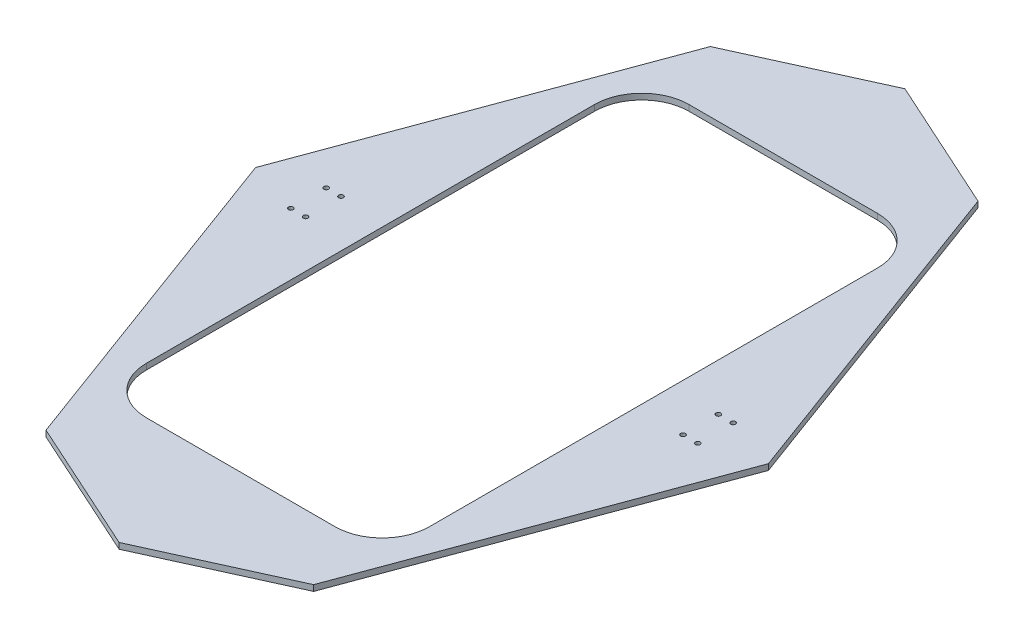
SolidWorks part; units mm, degrees
material "6061-T6 (SS)"
ref_plane "Front Plane" through (0, 0, 0) normal (0, 0, 1) x (1, 0, 0)
ref_plane "Top Plane" through (0, 0, 0) normal (0, 1, 0) x (1, 0, 0)
ref_plane "Right Plane" through (0, 0, 0) normal (1, 0, 0) x (0, 0, -1)
sketch "Sketch1" plane through (0, 0, 0) normal (0, 1, 0) x (1, 0, 0)
  line L0 (0, -292.1) -> (0, 292.1) construction
  line L5 (152.4, 0) -> (-152.4, 0) construction
  line L6 (203.2, 19.05) -> (219.075, -19.05) construction
  line L7 (101.6, -292.1) -> (-101.6, -292.1)
  line L8 (152.4, -241.3) -> (152.4, 241.3)
  line L9 (101.6, 292.1) -> (-101.6, 292.1)
  line L10 (-152.4, -241.3) -> (-152.4, 241.3)
  line L11 (-203.2, -19.05) -> (-219.075, -19.05) construction
  line L12 (-203.2, -19.05) -> (-203.2, 19.05) construction
  line L13 (-203.2, 19.05) -> (-219.075, 19.05) construction
  line L14 (-219.075, -19.05) -> (-219.075, 19.05) construction
  line L15 (-203.2, -19.05) -> (-219.075, 19.05) construction
  line L16 (-203.2, 19.05) -> (-219.075, -19.05) construction
  line L17 (203.2, -19.05) -> (219.075, 19.05) construction
  line L18 (219.075, -19.05) -> (219.075, 19.05) construction
  line L19 (203.2, 19.05) -> (219.075, 19.05) construction
  line L20 (203.2, -19.05) -> (203.2, 19.05) construction
  line L21 (203.2, -19.05) -> (219.075, -19.05) construction
  line L23 (-144.0827, -357.6619) -> (-276.108, 0)
  line L24 (0, -423.0411) -> (-144.0827, -357.6619)
  line L25 (144.0827, -357.6619) -> (0, -423.0411)
  line L26 (144.0827, -357.6619) -> (276.108, 0)
  line L27 (276.108, 0) -> (144.0827, 357.6619)
  line L28 (144.0827, 357.6619) -> (0, 423.0411)
  line L29 (-144.0827, 357.6619) -> (0, 423.0411)
  line L30 (-144.0827, 357.6619) -> (-276.108, 0)
  line L39 (-144.0827, -357.6619) -> (144.0827, -357.6619) construction
  line L40 (-144.0827, -357.6619) -> (-144.0827, 357.6619) construction
  line L41 (-144.0827, 357.6619) -> (144.0827, 357.6619) construction
  line L42 (144.0827, -357.6619) -> (144.0827, 357.6619) construction
  line L43 (-144.0827, -357.6619) -> (144.0827, 357.6619) construction
  line L44 (-144.0827, 357.6619) -> (144.0827, -357.6619) construction
  circle A0 centre (-219.075, 19.05) radius 2.54
  circle A1 centre (-203.2, 19.05) radius 2.54
  circle A2 centre (-203.2, -19.05) radius 2.54
  circle A3 centre (-219.075, -19.05) radius 2.54
  arc A4 (101.6, -292.1) -> (152.4, -241.3) centre (101.6, -241.3) ccw
  arc A5 (-101.6, -292.1) -> (-152.4, -241.3) centre (-101.6, -241.3) cw
  arc A6 (152.4, 241.3) -> (101.6, 292.1) centre (101.6, 241.3) ccw
  arc A7 (-101.6, 292.1) -> (-152.4, 241.3) centre (-101.6, 241.3) ccw
  circle A8 centre (219.075, -19.05) radius 2.54
  circle A9 centre (203.2, -19.05) radius 2.54
  circle A10 centre (203.2, 19.05) radius 2.54
  circle A11 centre (219.075, 19.05) radius 2.54
  point P0 (-211.1375, 0)
  point P31 (-152.4, -292.1)
  point P34 (152.4, 292.1)
  point P37 (-152.4, 292.1)
  point P41 (211.1375, 0)
  point P50 (0, 0)
  dimension "D7" = 15.875
  dimension "D10" = 50.8
  dimension "D11" = 288.1655
  dimension "D5" = 5.08
  dimension "D2" = 203.2
  dimension "D3" = 304.8
  dimension "D4" = 584.2
  dimension "D6" = 38.1
  dimension "D8" = 423.0411
  dimension "D9" = 276.108
  dimension "D12" = 715.3237
extrude "Boss-Extrude1" add sketch "Sketch1" along normal mid plane 6.35 contours A7 L9 A6 L8 A4 L7 A5 L10 region at (-200.6171, 0, 175.3322)
